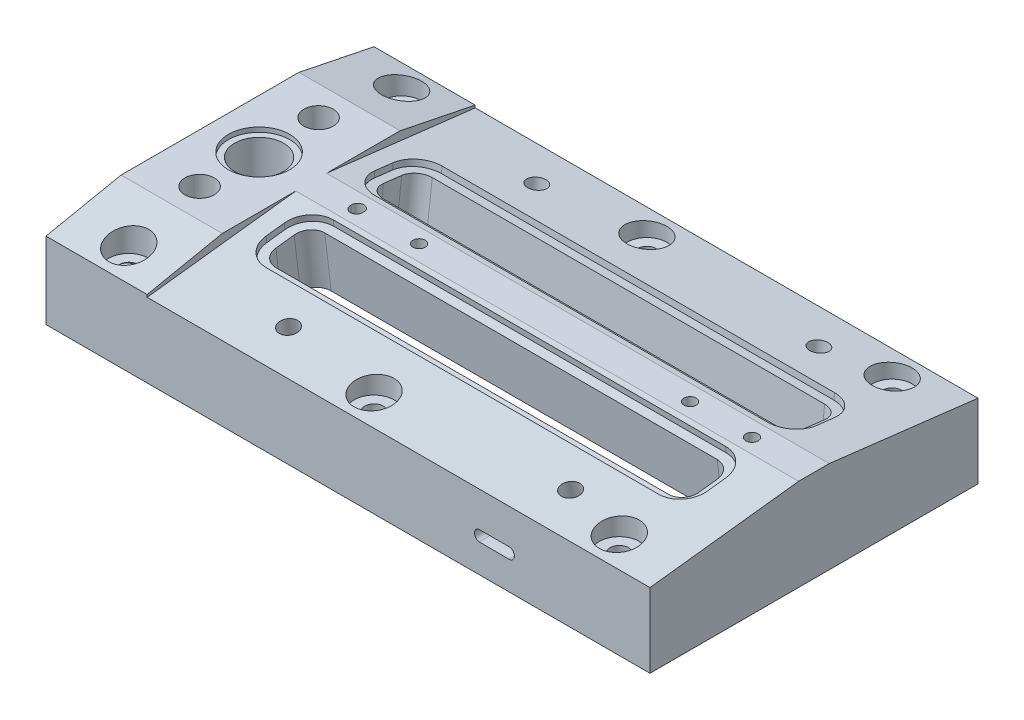
SolidWorks part; units mm, degrees
material "Custom Plastic"
ref_plane "Front Plane" through (0, 0, 0) normal (0, 0, 1) x (1, 0, 0)
ref_plane "Top Plane" through (0, 0, 0) normal (0, 1, 0) x (1, 0, 0)
ref_plane "Right Plane" through (0, 0, 0) normal (1, 0, 0) x (0, 0, -1)
sketch "Sketch1" plane through (0, 0, 0) normal (0, 1, 0) x (1, 0, 0)
  line L1 (0, 0) -> (197, 0)
  line L2 (0, 0) -> (0, 107)
  line L3 (0, 107) -> (197, 107)
  line L4 (197, 0) -> (197, 107)
  dimension "D1" = 197
  dimension "D2" = 107
extrude "Boss-Extrude1" add sketch "Sketch1" along normal blind 30
ref_plane "Left" through (197, 0, 0) normal (1, 0, 0) x (0, 0, -1)
ref_plane "Bot" through (0, 30, 0) normal (0, 1, 0) x (1, 0, 0)
ref_plane "der loco" through (0, 0, -51) normal (0, 0, -1) x (-1, 0, 0)
sketch "Sketch4" plane through (0, 0, 0) normal (0, 1, 0) x (1, 0, 0)
  line L0 (0, 107) -> (0, 0) construction
  line L1 (7.5, 31) -> (189.5, 31)
  line L2 (7.5, 31) -> (7.5, 76)
  line L3 (7.5, 76) -> (189.5, 76)
  line L4 (189.5, 31) -> (189.5, 76)
  line L5 (0, 0) -> (197, 0) construction
  dimension "D1" = 182
  dimension "D2" = 7.5
  dimension "D3" = 45
  dimension "D4" = 31
extrude "Cut-Extrude2" cut sketch "Sketch4" along normal blind 10
ref_plane "Plane32" through (0, 10, 0) normal (0, -1, 0) x (-1, 0, 0)
sketch "Sketch5" plane through (197, 0, 0) normal (1, 0, 0) x (0, 0, -1)
  line L0 (58.5, 30) -> (107, 24.2167)
  line L1 (0, 30) -> (107, 30) construction
  line L2 (107, 24.2167) -> (107, 30)
  line L3 (107, 30) -> (58.5, 30)
  line L4 (107, 30) -> (107, 0) construction
  dimension "D1" = 6.8
  dimension "D2" = 48.5
extrude "Cut-Extrude3" cut sketch "Sketch5" against normal blind 164
ref_plane "Plane24" through (0, 10, 0) normal (0, -1, 0) x (-1, 0, 0)
sketch "Sketch53" plane through (0, 10, 0) normal (0, -1, 0) x (-1, 0, 0)
  line L0 (-7.5, 51) -> (-7.5, 31)
  line L1 (-7.5, 76) -> (-7.5, 31) construction
  line L2 (-7.5, 31) -> (-38.5, 31)
  line L3 (-7.5, 31) -> (-189.5, 31) construction
  line L4 (-38.5, 31) -> (-7.5, 51)
  line L5 (-7.5, 53.5) -> (-189.5, 53.5) construction
  line L6 (-189.5, 31) -> (-189.5, 76) construction
  line L7 (-7.5, 56) -> (-7.5, 76)
  line L8 (-7.5, 76) -> (-38.5, 76)
  line L9 (-38.5, 76) -> (-7.5, 56)
  dimension "D1" = 31
  dimension "D2" = 20
extrude "Boss-Extrude11" add sketch "Sketch53" along normal up to surface (10 mm away) up to face at (98.5, 0, -53.5)
ref_plane "izq loco" through (0, 0, -56) normal (0, 0, -1) x (-1, 0, 0)
sketch "Sketch18" plane through (197, 0, 0) normal (1, 0, 0) x (0, 0, -1)
  line L0 (0, 24.2167) -> (0, 30)
  line L1 (0, 30) -> (0, 0) construction
  line L2 (0, 30) -> (48.5, 30)
  line L3 (48.5, 30) -> (0, 24.2167)
  line L4 (0, 30) -> (58.5, 30) construction
  dimension "D1" = 48.5
  dimension "D2" = 6.8
extrude "Cut-Extrude12" cut sketch "Sketch18" against normal up to surface (164 mm away) up to face at (33, 28.0722, -90.8333)
sketch "Sketch60" plane through (0, 0, 0) normal (0, 1, 0) x (1, 0, 0)
  point P0 (7.5, 31)
  point P1 (38.5, 31)
  point P2 (7.5, 76)
  point P6 (38.5, 76)
  dimension "D1" = 20
  dimension "D2" = 31
  dimension "D3" = 20
  dimension "D4" = 31
ref_axis "Axis6" through (7.5, 0, -31) along (1, 0, 0)
sketch "Sketch69" plane through (0, 10, 0) normal (0, -1, 0) x (-1, 0, 0)
  point P0 (-38.5, 56)
  point P1 (-7.5, 51)
  point P2 (-37.5, 51)
  point P3 (-7.5, 56)
  dimension "D1" = 31
  dimension "D2" = 20
  dimension "D3" = 20
  dimension "D4" = 30
sketch "der loco axis" plane through (0, 0, -51) normal (0, 0, -1) x (-1, 0, 0)
  point P0 (-7.5, 8.5)
  point P1 (-37.5, 8.5)
  dimension "D1" = 1.5
sketch "izq loco axis" plane through (0, 0, -56) normal (0, 0, -1) x (-1, 0, 0)
  line L0 (-38.5, 0) -> (-38.5, 10) construction
  line L1 (-7.5, 0) -> (-7.5, 10) construction
  point P0 (-7.5, 8.5)
  point P1 (-38.5, 8.5)
  dimension "D1" = 1.5
ref_plane "Plane3" through (0, 36.4573, -4.3473) normal (0, 0.993, -0.1184) x (1, 0, 0)
ref_axis "Axis8" through (38.5, 0, -76) along (-1, 0, 0)
ref_axis "Axis9" through (7.5, 8.5, -56) along (1, 0, 0)
ref_axis "Axis10" through (37.5, 8.5, -51) along (-1, 0, 0)
ref_plane "Izq bueno" through (0, 27.3584, -11.6273) normal (0, 0.9203, -0.3911) x (1, 0, 0)
sketch "Izq" plane through (0, 27.3584, -11.6273) normal (0, 0.9203, -0.3911) x (1, 0, 0)
  line L0 (7.5, 48.2138) -> (38.5, 69.9451)
  line L1 (38.5, 69.9451) -> (7.5, 69.9451)
  line L2 (7.5, 69.9451) -> (7.5, 48.2138)
extrude "Cut-Extrude28" cut sketch "Izq" against normal blind 14.5
ref_plane "Der bueno" through (0, -11.1593, -4.7427) normal (0, 0.9203, 0.3911) x (1, 0, 0)
sketch "Der" plane through (0, -11.1593, -4.7427) normal (0, 0.9203, 0.3911) x (1, 0, 0)
  line L0 (7.5, 50.2616) -> (38.5, 28.5303)
  line L1 (38.5, 28.5303) -> (7.5, 28.5303)
  line L2 (7.5, 28.5303) -> (7.5, 50.2616)
sketch "Sketch6" plane through (0, 36.4573, -4.3473) normal (0, 0.993, -0.1184) x (1, 0, 0)
  line L0 (197, 54.5364) -> (197, 103.38) construction
  line L1 (47, 75.4137) -> (175, 75.4137)
  line L2 (42, 70.4137) -> (42, 64.38)
  line L3 (47, 59.38) -> (175, 59.38)
  line L4 (180, 70.4137) -> (180, 64.38)
  line L13 (33, 103.38) -> (197, 103.38) construction
  arc A0 (175, 75.4137) -> (180, 70.4137) centre (175, 70.4137) cw
  arc A1 (175, 59.38) -> (180, 64.38) centre (175, 64.38) ccw
  arc A2 (42, 64.38) -> (47, 59.38) centre (47, 64.38) ccw
  arc A3 (47, 75.4137) -> (42, 70.4137) centre (47, 70.4137) ccw
  point P12 (180, 67.3968)
  dimension "D1" = 5
  dimension "D2" = 138
  dimension "D3" = 6.0337
  dimension "D4" = 17
  dimension "D5" = 44
sketch "Sketch7" plane through (0, 0, 0) normal (1, 0, 0) x (0, 0, -1)
  line L1 (107, 30) -> (107, 0) construction
  line L2 (107, 30) -> (0, 30) construction
  line L3 (107, 30) -> (107, 25)
  line L5 (107, 25) -> (82.5051, 30)
  line L6 (107, 30) -> (82.5051, 30)
  line L7 (0, 25) -> (0, 30)
  line L8 (0, 30) -> (0, 0) construction
  line L9 (0, 30) -> (24.4949, 30)
  line L10 (24.4949, 30) -> (0, 25)
  dimension "D1" = 25
  dimension "D2" = 25
  dimension "D3" = 25
  dimension "D4" = 25
extrude "Cut-Extrude5" cut sketch "Sketch7" along normal through all
sketch "Sketch9" plane through (0, 30, 0) normal (0, 1, 0) x (1, 0, 0)
  line L0 (0, 82.5051) -> (0, 24.4949) construction
  circle A0 centre (16, 53.5) radius 8
  point P6 (0, 53.5)
  dimension "D1" = 16
  dimension "D2" = 16
extrude "Cut-Extrude6" cut sketch "Sketch9" against normal blind 171
sketch "Sketch10" plane through (0, 30, 0) normal (0, 1, 0) x (1, 0, 0)
  circle A0 centre (16, 53.5) radius 10
  dimension "D1" = 20
extrude "Cut-Extrude7" cut sketch "Sketch10" against normal blind 1.5
sketch "Sketch11" plane through (0, 30, 0) normal (0, 1, 0) x (1, 0, 0)
  line L0 (33, 82.5051) -> (0, 82.5051) construction
  line L1 (16, 61.5) -> (16, 53.5) construction
  line L2 (33, 24.4949) -> (0, 24.4949) construction
  circle A0 centre (16, 72.9051) radius 4.8
  circle A1 centre (16, 34.0949) radius 4.8
  circle A6 centre (16, 53.5) radius 8 construction
  dimension "D1" = 9.6
  dimension "D3" = 9.6
  dimension "D2" = 9.6
  dimension "D4" = 9.6
extrude "Cut-Extrude8" cut sketch "Sketch11" against normal blind 12.5
sketch "Sketch12" plane through (0, 30, 0) normal (0, 1, 0) x (1, 0, 0)
  line L0 (0, 82.5051) -> (0, 107) construction
  line L2 (33, 107) -> (0, 107) construction
  line L3 (33, 0) -> (0, 0) construction
  circle A0 centre (18, 98) radius 3
  circle A1 centre (98, 9) radius 3
  circle A2 centre (178, 9) radius 3
  circle A3 centre (18, 9) radius 3
  circle A4 centre (98, 98) radius 3
  circle A5 centre (178, 98) radius 3
  dimension "D2" = 6
  dimension "D7" = 80
  dimension "D8" = 18
  dimension "D9" = 80
  dimension "D10" = 9
  dimension "D11" = 9
extrude "Cut-Extrude9" cut sketch "Sketch12" against normal through all
sketch "Sketch13" plane through (0, 36.4573, -4.3473) normal (0, 0.993, -0.1184) x (1, 0, 0)
  line L0 (33, 54.5364) -> (33, 103.38) construction
  line L1 (33, 103.38) -> (197, 103.38) construction
  line L2 (197, 54.5364) -> (197, 103.38) construction
  circle A0 centre (66, 90.38) radius 3
  circle A1 centre (158, 90.38) radius 3
  dimension "D1" = 6
  dimension "D4" = 6
  dimension "D2" = 33
  dimension "D3" = 13
  dimension "D5" = 39
extrude "Cut-Extrude10" cut sketch "Sketch13" against normal blind 16.5
ref_plane "Plane8" through (0, 24, 4.899) normal (0, 0.9798, 0.2) x (1, 0, 0)
sketch "Sketch14" plane through (0, 24, 4.899) normal (0, 0.9798, 0.2) x (1, 0, 0)
  line L0 (33, 5) -> (0, 5) construction
  line L1 (33, 63.3181) -> (33, 109.6815) construction
  line L2 (197, 5) -> (197, 30) construction
  circle A0 centre (66, 18) radius 3
  circle A1 centre (158, 18) radius 3
  dimension "D1" = 6
  dimension "D2" = 6
  dimension "D3" = 13
  dimension "D4" = 33
  dimension "D5" = 39
extrude "Cut-Extrude11" cut sketch "Sketch14" against normal blind 26.5
ref_plane "Plane9" through (0, 23.8772, 2.8472) normal (0, 0.993, 0.1184) x (1, 0, 0)
sketch "Sketch23" plane through (0, 23.8772, 2.8472) normal (0, 0.993, 0.1184) x (1, 0, 0)
  line L0 (33, 2.8674) -> (197, 2.8674) construction
  line L1 (47, 46.8674) -> (175, 46.8674)
  line L2 (42, 41.8674) -> (42, 35.8674)
  line L3 (47, 30.8674) -> (175, 30.8674)
  line L4 (180, 41.8674) -> (180, 35.8674)
  line L5 (197, 2.8674) -> (197, 51.7109) construction
  arc A0 (175, 46.8674) -> (180, 41.8674) centre (175, 41.8674) cw
  arc A1 (175, 30.8674) -> (180, 35.8674) centre (175, 35.8674) ccw
  arc A2 (42, 35.8674) -> (47, 30.8674) centre (47, 35.8674) ccw
  arc A3 (47, 46.8674) -> (42, 41.8674) centre (47, 41.8674) ccw
  point P10 (180, 46.8674)
  point P15 (42, 30.8674)
  point P18 (42, 46.8674)
  dimension "D5" = 5
  dimension "D1" = 138
  dimension "D2" = 16
  dimension "D3" = 44
  dimension "D4" = 17
extrude "Cut-Extrude14" cut sketch "Sketch23" against normal blind 35
extrude "Cut-Extrude15" cut sketch "Sketch6" against normal blind 130
sketch "Sketch41" plane through (0, 0, 0) normal (0, 1, 0) x (1, 0, 0)
  line L0 (197, 0) -> (197, 107) construction
  line L1 (197, 107) -> (0, 107) construction
  line L2 (0, 0) -> (197, 0) construction
  circle A0 centre (138.5, 9) radius 3
  circle A1 centre (138.5, 98) radius 3
  dimension "D1" = 6
  dimension "D4" = 6
  dimension "D2" = 58.5
  dimension "D3" = 58.5
  dimension "D5" = 9
  dimension "D6" = 9
extrude "Cut-Extrude21" cut sketch "Sketch41" along normal blind 8
sketch "Sketch42" plane through (0, 0, 0) normal (0, 0, 1) x (1, 0, 0)
  line L0 (197, 24.2167) -> (197, 0) construction
  line L5 (0, 0) -> (197, 0) construction
  line L6 (141.2615, 12.7727) -> (151, 12.7727)
  line L7 (141.2615, 9.2727) -> (151, 9.2273)
  arc A0 (141.2615, 12.7727) -> (141.2615, 9.2727) centre (141.5457, 11.0227) ccw
  arc A2 (151, 12.7727) -> (151, 9.2273) centre (151, 11) cw
  dimension "D4" = 0.268
  dimension "D2" = 1.7727
  dimension "D3" = 1.7729
  dimension "D1" = 9.7385
  dimension "D5" = 46
  dimension "D6" = 11
extrude "Cut-Extrude22" cut sketch "Sketch42" against normal blind 10
ref_plane "Plane19" through (0, 0, -107) normal (0, 0, -1) x (-1, 0, 0)
sketch "Sketch43" plane through (0, 0, -107) normal (0, 0, -1) x (-1, 0, 0)
  line L0 (-55.7, 11) -> (-46, 11) construction
  line L1 (-55.7, 12.8) -> (-46, 12.8)
  line L2 (-55.7, 9.2) -> (-46, 9.2)
  line L3 (-197, 0) -> (0, 0) construction
  line L4 (0, 25) -> (0, 0) construction
  arc A0 (-55.7, 12.8) -> (-55.7, 9.2) centre (-55.7, 11) ccw
  arc A1 (-46, 9.2) -> (-46, 12.8) centre (-46, 11) ccw
  point P2 (-50.85, 11)
  dimension "D2" = 1.8
  dimension "D1" = 9.7
  dimension "D3" = 11
  dimension "D4" = 46
extrude "Cut-Extrude23" cut sketch "Sketch43" against normal blind 10
extrude "Cut-Extrude29" cut sketch "Der" against normal blind 14.5
sketch "Sketch75" plane through (0, 30, 0) normal (0, 1, 0) x (1, 0, 0)
  line L2 (197, 48.5) -> (197, 58.5) construction
  line L3 (47, 63.3095) -> (175, 63.3095) construction
  line L4 (175, 43.6905) -> (47, 43.6905) construction
  circle A0 centre (177, 53.2824) radius 2
  circle A1 centre (156.799, 53.2824) radius 2
  circle A2 centre (68, 53.6905) radius 2
  circle A3 centre (48, 53.6905) radius 2
  dimension "D1" = 4
  dimension "D2" = 4
  dimension "D3" = 4
  dimension "D4" = 4
  dimension "D5" = 20.201
  dimension "D6" = 20
  dimension "D7" = 20
  dimension "D8" = 10.0271
  dimension "D9" = 10
  dimension "D10" = 15
extrude "Cut-Extrude30" cut sketch "Sketch75" against normal blind 7.5
sketch "Sketch76" plane through (0, 0, 0) normal (0, 1, 0) x (1, 0, 0)
  circle A0 centre (48, 53.2824) radius 2
  circle A1 centre (177, 53.2824) radius 2
  dimension "D1" = 4
  dimension "D2" = 4
extrude "Cut-Extrude31" cut sketch "Sketch76" along normal blind 61.5
sketch "Sketch77" plane through (0, 23.8772, 2.8472) normal (0, 0.993, 0.1184) x (1, 0, 0)
  line L25 (183, 35.8674) -> (183, 41.8674)
  line L26 (175, 49.8674) -> (47, 49.8674)
  line L27 (47, 27.8674) -> (175, 27.8674)
  line L28 (39, 41.8674) -> (39, 35.8674)
  line L29 (183, 35.8674) -> (183, 41.8674)
  line L30 (175, 49.8674) -> (47, 49.8674)
  line L31 (47, 27.8674) -> (175, 27.8674)
  line L32 (39, 41.8674) -> (39, 35.8674)
  arc A19 (175, 27.8674) -> (183, 35.8674) centre (175, 35.8674) ccw
  arc A20 (183, 41.8674) -> (175, 49.8674) centre (175, 41.8674) ccw
  arc A21 (47, 49.8674) -> (39, 41.8674) centre (47, 41.8674) ccw
  arc A22 (39, 35.8674) -> (47, 27.8674) centre (47, 35.8674) ccw
  arc A23 (175, 27.8674) -> (183, 35.8674) centre (175, 35.8674) ccw
  arc A24 (183, 41.8674) -> (175, 49.8674) centre (175, 41.8674) ccw
  arc A25 (47, 49.8674) -> (39, 41.8674) centre (47, 41.8674) ccw
  arc A26 (39, 35.8674) -> (47, 27.8674) centre (47, 35.8674) ccw
  dimension "D1" = 3
extrude "Cut-Extrude32" cut sketch "Sketch77" against normal blind 2
sketch "Sketch78" plane through (0, 36.4573, -4.3473) normal (0, 0.993, -0.1184) x (1, 0, 0)
  line L31 (47, 56.38) -> (175, 56.38)
  line L32 (183, 64.38) -> (183, 70.4137)
  line L33 (175, 78.4137) -> (47, 78.4137)
  line L34 (39, 70.4137) -> (39, 64.38)
  line L35 (47, 56.38) -> (175, 56.38)
  line L36 (183, 64.38) -> (183, 70.4137)
  line L37 (175, 78.4137) -> (47, 78.4137)
  line L38 (39, 70.4137) -> (39, 64.38)
  arc A19 (183, 70.4137) -> (175, 78.4137) centre (175, 70.4137) ccw
  arc A20 (39, 64.38) -> (47, 56.38) centre (47, 64.38) ccw
  arc A21 (175, 56.38) -> (183, 64.38) centre (175, 64.38) ccw
  arc A22 (47, 78.4137) -> (39, 70.4137) centre (47, 70.4137) ccw
  arc A23 (183, 70.4137) -> (175, 78.4137) centre (175, 70.4137) ccw
  arc A24 (39, 64.38) -> (47, 56.38) centre (47, 64.38) ccw
  arc A25 (175, 56.38) -> (183, 64.38) centre (175, 64.38) ccw
  arc A26 (47, 78.4137) -> (39, 70.4137) centre (47, 70.4137) ccw
  dimension "D1" = 3
extrude "Cut-Extrude33" cut sketch "Sketch78" against normal blind 2
sketch "Sketch80" plane through (0, 36.4573, -4.3473) normal (0, 0.993, -0.1184) x (1, 0, 0)
  line L0 (42, 64.38) -> (42, 70.4137) construction
  line L1 (47, 76.3968) -> (175, 76.3968)
  line L2 (42, 71.3968) -> (42, 63.3968)
  line L3 (47, 58.3968) -> (175, 58.3968)
  line L4 (180, 71.3968) -> (180, 63.3968)
  line L5 (180, 70.4137) -> (180, 64.38) construction
  arc A0 (47, 76.3968) -> (42, 71.3968) centre (47, 71.3968) ccw
  arc A1 (42, 63.3968) -> (47, 58.3968) centre (47, 63.3968) ccw
  arc A2 (175, 58.3968) -> (180, 63.3968) centre (175, 63.3968) ccw
  arc A3 (175, 76.3968) -> (180, 71.3968) centre (175, 71.3968) cw
  point P4 (42, 67.3968)
  point P7 (42, 67.3968)
  point P8 (180, 67.3968)
  point P11 (180, 67.3968)
  dimension "D2" = 5
  dimension "D1" = 18
sketch "Sketch81" plane through (0, 23.8772, 2.8472) normal (0, 0.993, 0.1184) x (1, 0, 0)
  line L0 (180, 41.8674) -> (180, 35.8674) construction
  line L1 (47, 47.8674) -> (175, 47.8674)
  line L2 (42, 42.8674) -> (42, 34.8674)
  line L3 (47, 29.8674) -> (175, 29.8674)
  line L4 (180, 42.8674) -> (180, 34.8674)
  line L5 (42, 35.8674) -> (42, 41.8674) construction
  arc A0 (175, 29.8674) -> (180, 34.8674) centre (175, 34.8674) ccw
  arc A1 (175, 47.8674) -> (180, 42.8674) centre (175, 42.8674) cw
  arc A2 (47, 47.8674) -> (42, 42.8674) centre (47, 42.8674) ccw
  arc A3 (42, 34.8674) -> (47, 29.8674) centre (47, 34.8674) ccw
  point P4 (180, 38.8674)
  point P7 (180, 38.8674)
  point P8 (42, 38.8674)
  point P11 (42, 38.8674)
  dimension "D2" = 5
  dimension "D1" = 18
sketch "Sketch88" plane through (0, 30, 0) normal (0, 1, 0) x (1, 0, 0)
  line L0 (0, 53.5) -> (197, 53.5) construction
  line L1 (0, 82.5051) -> (0, 24.4949) construction
  line L2 (197, 48.5) -> (197, 58.5) construction
  circle A0 centre (18, 9) radius 6.5
  circle A1 centre (98, 9) radius 6.5
  circle A2 centre (178, 9) radius 6.5
  circle A3 centre (178, 98) radius 6.5
  circle A4 centre (98, 98) radius 6.5
  circle A5 centre (18, 98) radius 6.5
  dimension "D1" = 13
extrude "Cut-Extrude34" cut sketch "Sketch88" against normal blind 10
thread "Thread1" pitch 2 method extrude profile "Thread Profile2" start angle 0, offset 0, length 10, pitch 2, diameter 6
ref_plane "Plane34" through (15, 20, -9) normal (0, 0, 1) x (-1, 0, 0)
sketch "Thread Profile2" plane through (15, 20, -9) normal (0, 0, 1) x (-1, 0, 0)
  line L0 (0, 0) -> (0, 2) construction
  line L11 (0, 0) -> (0, 1.75)
  line L12 (0, 1.75) -> (-1.0825, 1.125)
  line L13 (-1.0825, 1.125) -> (-1.0825, 0.625)
  line L15 (-1.0825, 0.625) -> (0, 0)
  line L17 (-1.0825, 0.875) -> (0, 0.875) construction
  point P2 (0, 0)
  dimension "Pitch" = 2
  dimension "Profile_Angle" = 60
  dimension "Profile_Land" = 0.5
  dimension "Profile_Height" = 1.0825
